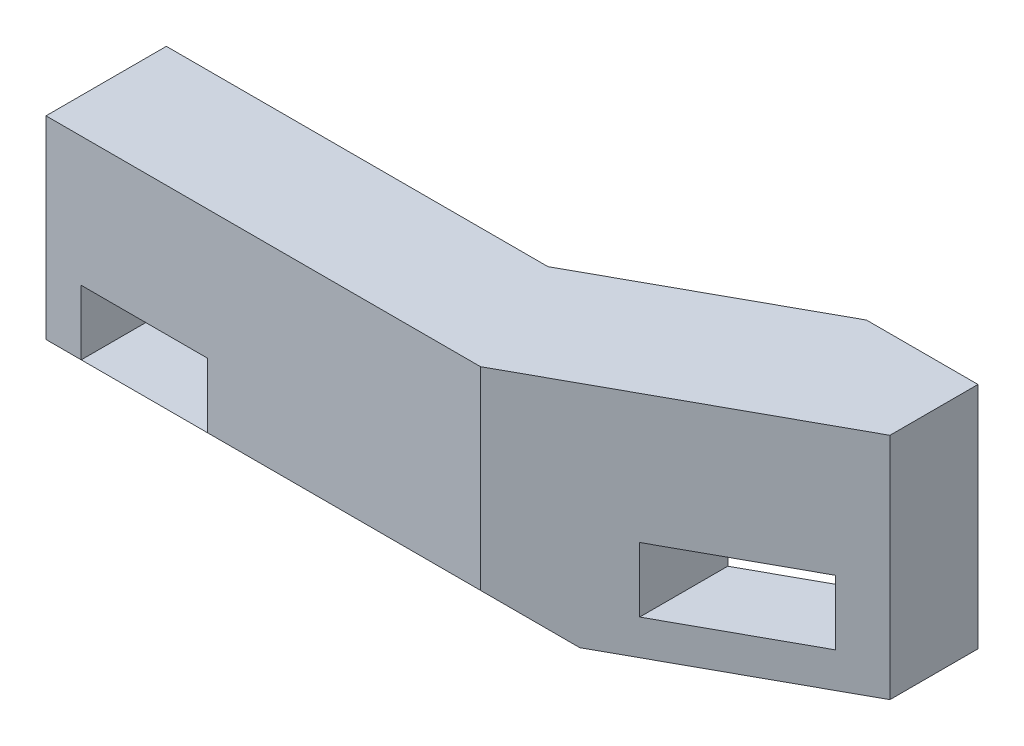
SolidWorks part; units mm, degrees
ref_plane "Front Plane" through (0, 0, 0) normal (0, 0, 1) x (1, 0, 0)
ref_plane "Top Plane" through (0, 0, 0) normal (0, 1, 0) x (1, 0, 0)
ref_plane "Right Plane" through (0, 0, 0) normal (1, 0, 0) x (0, 0, -1)
sketch "Sketch1" plane through (0, 0, 0) normal (0, 1, 0) x (1, 0, 0)
  line L0 (6.5, -2.05) -> (8.3, -2.05)
  line L1 (-6.5, -2.05) -> (6.5, -2.05)
  line L2 (-6.5, -2.05) -> (-6.5, 2.05)
  line L3 (-6.5, 2.05) -> (6.5, 2.05)
  line L4 (6.5, -2.05) -> (6.5, 2.05)
  line L5 (-6.5, -2.05) -> (6.5, 2.05) construction
  line L6 (-6.5, 2.05) -> (6.5, -2.05) construction
  line L7 (8.3, -2.05) -> (17.3, 2.8991)
  line L8 (17.3, 2.8991) -> (17.3, 5.8991)
  line L9 (6.5, 2.05) -> (13.4996, 5.8991)
  line L10 (13.4996, 5.8991) -> (17.3, 5.8991)
  point P0 (0, 0)
  dimension "D1" = 13
  dimension "D2" = 4.1
  dimension "D3" = 1.8
  dimension "D4" = 9
  dimension "D5" = 4.9491
  dimension "D6" = 3
extrude "Boss-Extrude1" add sketch "Sketch1" along normal mid plane 7.8 contours L10 L9 L4 L0 L7 L8 | L1 L4 L3 L2 region at (11.6578, 0, -2.2342) region at (0, 0, 0)
sketch "Sketch2" plane through (0, -3.9, 0) normal (0, -1, 0) x (1, 0, 0)
  line L0 (17.3, -5.8991) -> (8.3, -0.95)
  line L1 (8.3, -0.95) -> (6.5, -2.05)
  line L2 (8.3, 2.05) -> (17.3, -2.8991) construction
  line L3 (6.5, -2.05) -> (13.4996, -5.8991)
  line L4 (13.4996, -5.8991) -> (17.3, -5.8991)
  dimension "D1" = 0
extrude "Cut-Extrude1" cut sketch "Sketch2" against normal offset from surface (6.6 mm away) 1.2 up to face at (7.1285, 3.9, -2.0996)
sketch "Sketch3" plane through (0, 0, 2.05) normal (0, 0, 1) x (1, 0, 0)
  line L0 (-6.5, 3.9) -> (-6.5, -3.9) construction
  line L1 (-5.3, -0.5) -> (-1, -0.5)
  line L2 (-5.3, -0.5) -> (-5.3, -2.7)
  line L3 (-5.3, -2.7) -> (-1, -2.7)
  line L4 (-1, -0.5) -> (-1, -2.7)
  line L5 (-5.3, -0.5) -> (-1, -2.7) construction
  line L6 (-5.3, -2.7) -> (-1, -0.5) construction
  line L7 (-6.5, -3.9) -> (8.3, -3.9) construction
  line L8 (17.3, 3.9) -> (17.3, -3.9) construction
  line L9 (11.8, -0.5) -> (16.1, -0.5)
  line L10 (11.8, -0.5) -> (11.8, -2.7)
  line L11 (11.8, -2.7) -> (16.1, -2.7)
  line L12 (16.1, -0.5) -> (16.1, -2.7)
  line L13 (11.8, -0.5) -> (16.1, -2.7) construction
  line L14 (11.8, -2.7) -> (16.1, -0.5) construction
  line L15 (8.3, -3.9) -> (17.3, -3.9) construction
  point P0 (-3.15, -1.6)
  point P9 (13.95, -1.6)
  dimension "D1" = 2.2
  dimension "D2" = 4.3
  dimension "D3" = 1.2
  dimension "D4" = 1.2
  dimension "D5" = 4.3
  dimension "D6" = 2.2
  dimension "D7" = 1.2
  dimension "D8" = 1.2
extrude "Cut-Extrude2" cut sketch "Sketch3" against normal through all both and the other way through all
chamfer "Chamfer1" distance 1.2 angle 45 1 edges at (0.9, -3.9, 2.05)
